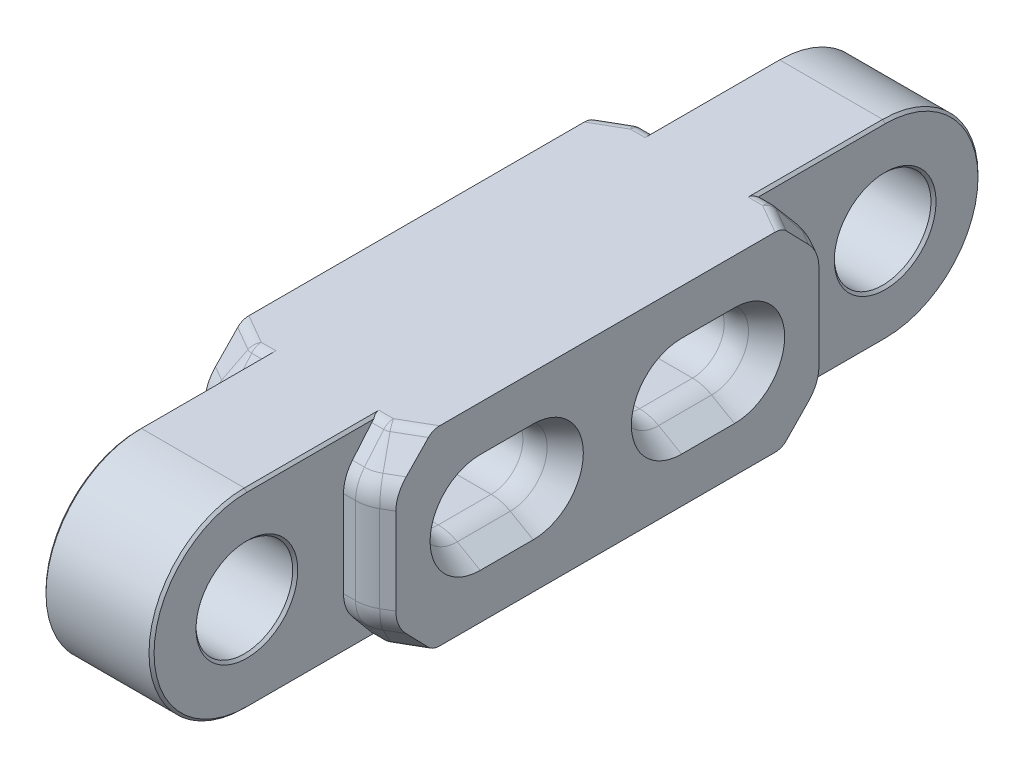
SolidWorks part; units mm, degrees
ref_plane "Front Plane" through (0, 0, 0) normal (1, 0, 0) x (0, 1, 0)
ref_plane "Top Plane" through (0, 0, 0) normal (0, 0, 1) x (0, 1, 0)
ref_plane "Right Plane" through (0, 0, 0) normal (0, 1, 0) x (-1, 0, 0)
sketch "Sketch1" plane through (0, 0, 0) normal (1, 0, 0) x (0, 1, 0)
  line L0 (-15, 0) -> (-15, -100.4)
  line L1 (-15, -50.2) -> (15, -50.2) construction
  line L2 (15, -100.4) -> (15, 0)
  line L3 (-5, -30.2) -> (-5, -38.5333)
  line L4 (-15, -85.2) -> (15, -85.2)
  line L6 (-15, -15.2) -> (15, -15.2)
  line L7 (0, 15) -> (0, -50.2)
  circle A0 centre (0, 0) radius 7.6
  circle A1 centre (0, 0) radius 15
  circle A26 centre (0, -100.4) radius 15
  circle A27 centre (0, -100.4) radius 7.6
  circle A28 centre (0, -38.5333) radius 5
  circle A29 centre (0, -30.2) radius 5
  point P16 (-5, -38.5333)
  point P17 (0, -43.5333)
  point P20 (0, -25.2)
  dimension "D1" = 30
  dimension "D2" = 15.2
  dimension "D3" = 15.2
  dimension "D4" = 70
  dimension "D5" = 10
  dimension "D6" = 6.6667
  dimension "D7" = 10
extrude "Boss-Extrude1" add sketch "Sketch1" along normal blind 8.5 contours L7 A1 A0 | A1 L0 L6 L7 | L0 L1 L7 L6 region at (0, -11.4068, -11.8513) region at (0, -10.3694, 10.3694) region at (0, -8.4447, -32.3962)
extrude "Boss-Extrude2" add sketch "Sketch1<4>" along normal blind 15 contours L0 L1 L7 L6 region at (0, -8.4447, -32.3962)
sketch "Sketch1<4>" plane through (0, 0, 0) normal (1, 0, 0) x (0, 1, 0) same geometry as "Sketch1"
chamfer "Chamfer8" distance 3 angle 30 1 edges at (15, -7.5, -15.2) first distance on face at (11.75, -7.5, -15.2)
fillet "Fillet6" radius 6 1 edges at (12, -7.5, -15.2)
chamfer "Chamfer9" distance 6 angle 40 3 edges at (14.1962, -15, -16.4679) (11.9452, -15, -15.4044) (9.4462, -15, -15.2) first distance on face at (14.1962, -7.5, -16.4679) first distance on face at (11.9188, -7.5, -15.5032) first distance on face at (9.4462, -7.5, -15.2)
fillet "Fillet7" radius 6 3 edges at (14.1962, -9, -16.4679) (11.9452, -9, -15.4044) (9.4462, -9, -15.2)
chamfer "Chamfer10" distance 5 angle 30 3 edges at (15, -3.5355, -42.0689) (15, -5, -34.3667) (15, -3.5355, -26.6645) first distance on face at (7.5, -3.0178, -41.5511) first distance on face at (7.5, -5, -34.3667) first distance on face at (7.5, -3.0178, -27.1822)
fillet "Fillet8" radius 6 3 edges at (10, -3.5355, -42.0689) (10, -5, -34.3667) (10, -3.5355, -26.6645)
fillet "Fillet9" radius 2 3 edges at (9.4462, -15, -20.2346) (10.6422, -15, -20.2675) (12.9375, -15, -21.5547)
chamfer "Chamfer11" distance 0.4 angle 45 3 edges at (8.5, -7.6, 0) (8.5, -15, -10.5836) (8.5, -10.6066, 10.6066)
mirror "Mirror1" about plane through (8.5, 0, 0) normal (0, 1, 0) of bodies 102
mirror "Mirror2" about plane through (8.5, 0, -50.2) normal (0, 0, 1) of bodies 108
mirror "Mirror3" about plane through (0, 0, 0) normal (1, 0, 0) of bodies 109
equation "\"D6@Sketch1\"=\"D5@Sketch1\"*2/3"
equation "\"D7@Sketch1\"=\"D5@Sketch1\""
